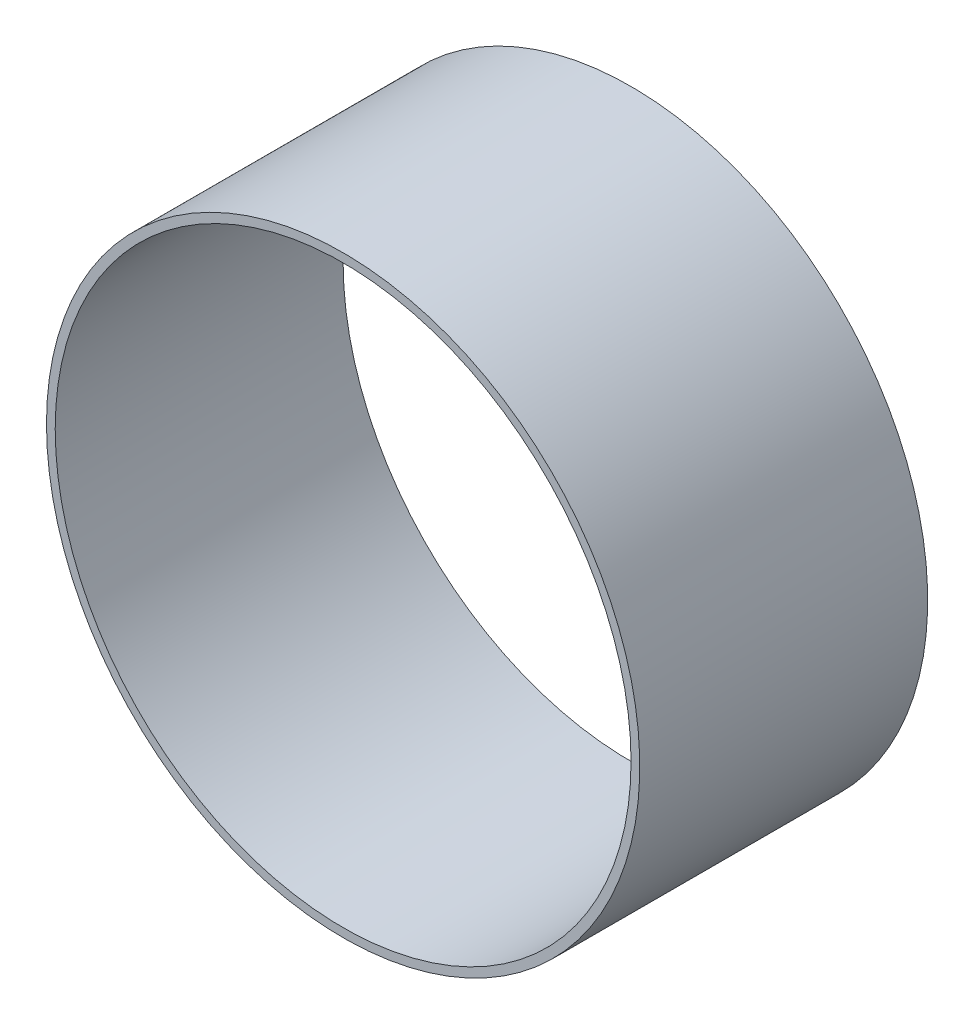
SolidWorks part; units mm, degrees
ref_plane "Front Plane" through (0, 0, 0) normal (0, 0, 1) x (1, 0, 0)
ref_plane "Top Plane" through (0, 0, 0) normal (0, 1, 0) x (1, 0, 0)
ref_plane "Right Plane" through (0, 0, 0) normal (1, 0, 0) x (0, 0, -1)
sketch "Sketch1" plane through (0, 0, 0) normal (0, 0, 1) x (1, 0, 0)
  circle A0 centre (0, 0) radius 39.2557
  circle A1 centre (0, 0) radius 38.1
  dimension "D1" = 76.2
  dimension "D2" = 78.5114
extrude "Boss-Extrude1" add sketch "Sketch1" along normal mid plane 38.1
equation "\"AIRFRAME_OD\"= 3.091in"
equation "\"AIRFRAME_ID\"= 3.00in"
equation "\"FLAT_T\"= 0.125in"
equation "\"NOSE_EXP_L\"= 3.5in"
equation "\"NOSE_SHOULDER_L\"= 5in"
equation "\"MAIN_L\"= 30in"
equation "\"RECO_COUP_L\"= 6in"
equation "\"RECO_SWITCH_L\"= 1.5in"
equation "\"DROGUE_L\"= 14in"
equation "\"ATS_FORE_COUP_L\"= 4in"
equation "\"ATS_AFT_COUP_L\"= 2.5in"
equation "\"LOWER_L\"= 16in"
equation "\"FIN_N\"= 4"
equation "\"CR_AFT_X\"= 0.5in"
equation "\"CR_FORE_X\"= 6in"
equation "\"D1@Sketch1\"=\"AIRFRAME_ID\""
equation "\"D2@Sketch1\"=\"AIRFRAME_OD\""
equation "\"D1@Boss-Extrude1\"=\"RECO_SWITCH_L\""
equation "\"FIN_ROOT\"= 5in"
equation "\"FIN_X\"= 0.75in"
equation "\"MOTOR_OD\"= 2.25in"
equation "\"MOTOR_ID\"= 2.126in"
